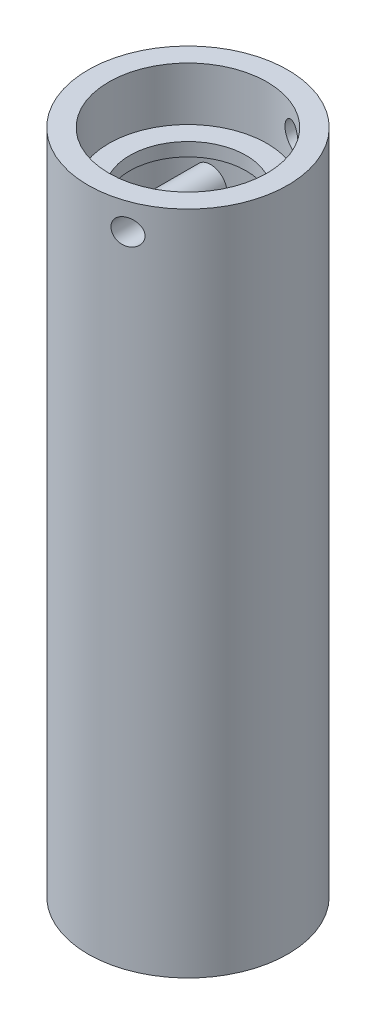
SolidWorks part; units mm, degrees
ref_plane "Front Plane" through (0, 0, 0) normal (0, 0, 1) x (1, 0, 0)
ref_plane "Top Plane" through (0, 0, 0) normal (0, 1, 0) x (1, 0, 0)
ref_plane "Right Plane" through (0, 0, 0) normal (1, 0, 0) x (0, 0, -1)
sketch "Sketch1" plane through (0, 0, 0) normal (0, 1, 0) x (1, 0, 0)
  circle A0 centre (0, 0) radius 19.05
  dimension "D1" = 38.1
extrude "Boss-Extrude1" add sketch "Sketch1" along normal mid plane 127
sketch "Sketch2" plane through (0, -63.5, 0) normal (0, -1, 0) x (1, 0, 0)
  circle A0 centre (0, 0) radius 14.2875
  dimension "D1" = 28.575
extrude "Cut-Extrude1" cut sketch "Sketch2" against normal blind 114.3
sketch "Sketch3" plane through (0, 63.5, 0) normal (0, 1, 0) x (1, 0, 0)
  circle A0 centre (0, 0) radius 11.1125
  circle A2 centre (0, 0) radius 14.2875 construction
  circle A3 centre (0, 0) radius 14.2875 construction
  dimension "D1" = 3.175
extrude "Cut-Extrude3" cut sketch "Sketch3" against normal through all
sketch "Sketch4" plane through (0, 63.5, 0) normal (0, 1, 0) x (1, 0, 0)
  line L0 (0, 11.1125) -> (0, 19.05) construction
  circle A0 centre (0, 0) radius 15.0813
  circle A1 centre (0, 0) radius 11.1125 construction
  circle A2 centre (0, 0) radius 19.05 construction
  point P10 (0, 15.0813)
extrude "Cut-Extrude5" cut sketch "Sketch4" against normal blind 10.16 and the other way through all
sketch "Sketch6" plane through (0, 0, 0) normal (0, 0, 1) x (1, 0, 0)
  line L0 (19.05, -63.5) -> (19.05, 63.5) construction
  line L1 (19.05, 63.5) -> (-19.05, 63.5) construction
  circle A0 centre (6.35, 58.42) radius 3.175
  dimension "D2" = 6.35
  dimension "D1" = 12.7
  dimension "D3" = 5.08
extrude "Boss-Extrude2" add sketch "Sketch6" along normal up to surface (11.6927 mm away) up to face at (0, 63.5, 15.0813)
sketch "Sketch8" plane through (0, 0, 0) normal (0, 0, 1) x (1, 0, 0)
  circle A0 centre (6.35, 58.42) radius 3.175 construction
  circle A1 centre (6.35, 58.42) radius 3.175 construction
  circle A2 centre (6.35, 58.42) radius 2.4
  dimension "D1" = 4.8
extrude "Cut-Extrude6" cut sketch "Sketch8" against normal through all both and the other way through all
sketch "Sketch9" plane through (0, 63.5, 0) normal (0, 1, 0) x (1, 0, 0)
  line L0 (3.175, 0) -> (3.175, -14.7433) construction
  line L1 (3.175, -2.032) -> (9.525, -2.032)
  line L2 (3.175, -2.032) -> (3.175, 2.032)
  line L3 (3.175, 2.032) -> (9.525, 2.032)
  line L4 (9.525, -2.032) -> (9.525, 2.032)
  line L5 (3.175, -2.032) -> (9.525, 2.032) construction
  line L6 (3.175, 2.032) -> (9.525, -2.032) construction
  line L7 (9.525, -11.6927) -> (9.525, 0) construction
  point P0 (6.35, 0)
  dimension "D1" = 4.064
extrude "Cut-Extrude7" cut sketch "Sketch9" against normal through all both and the other way through all
